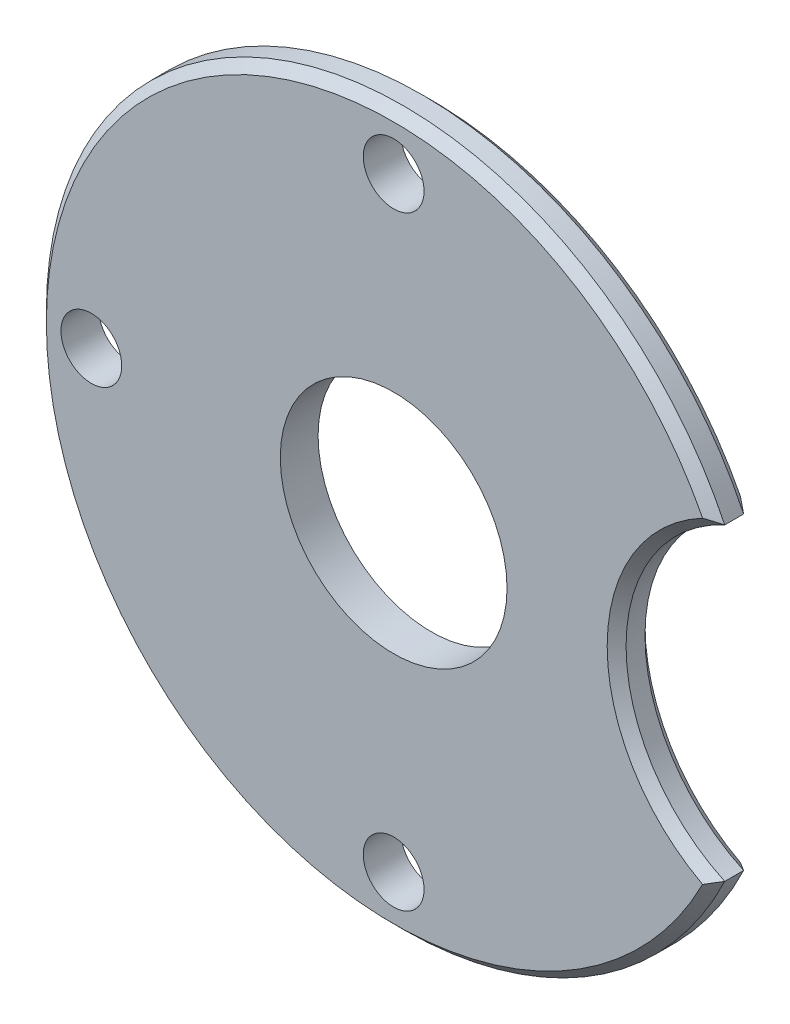
SolidWorks part; units mm, degrees
ref_plane "Front Plane" through (0, 0, 0) normal (0, 0, 1) x (1, 0, 0)
ref_plane "Top Plane" through (0, 0, 0) normal (0, 1, 0) x (1, 0, 0)
ref_plane "Right Plane" through (0, 0, 0) normal (1, 0, 0) x (0, 0, -1)
sketch "Sketch1" plane through (0, 0, 0) normal (0, 0, 1) x (1, 0, 0)
  line L0 (0, 0) -> (33.02, 0) construction
  circle A0 centre (0, 0) radius 29.972
  circle A1 centre (33.02, 0) radius 14.2875
  circle A2 centre (0, 0) radius 9.525
  circle A3 centre (0, 0) radius 25.4 construction
  circle A4 centre (0, 25.4) radius 2.5527
  circle A5 centre (-25.4, 0) radius 2.5527
  circle A6 centre (0, -25.4) radius 2.5527
  dimension "D1" = 59.944
  dimension "D3" = 28.575
  dimension "D4" = 19.05
  dimension "D5" = 50.8
  dimension "D6" = 5.1054
  dimension "D7" = 5.1054
  dimension "D8" = 5.1054
  dimension "D2" = 33.02
extrude "Boss-Extrude1" add sketch "Sketch1" along normal blind 3.175 contours A1 A0 A6 A5 A4 A2 region at (17.9054, 0, 0)
chamfer "Chamfer1" distance 0.7937 angle 45 2 edges at (18.7325, 0, 3.175) (-29.972, 0, 3.175)
chamfer "Chamfer2" distance 0.7937 angle 45 2 edges at (18.7325, 0, 0) (-29.972, 0, 0)
